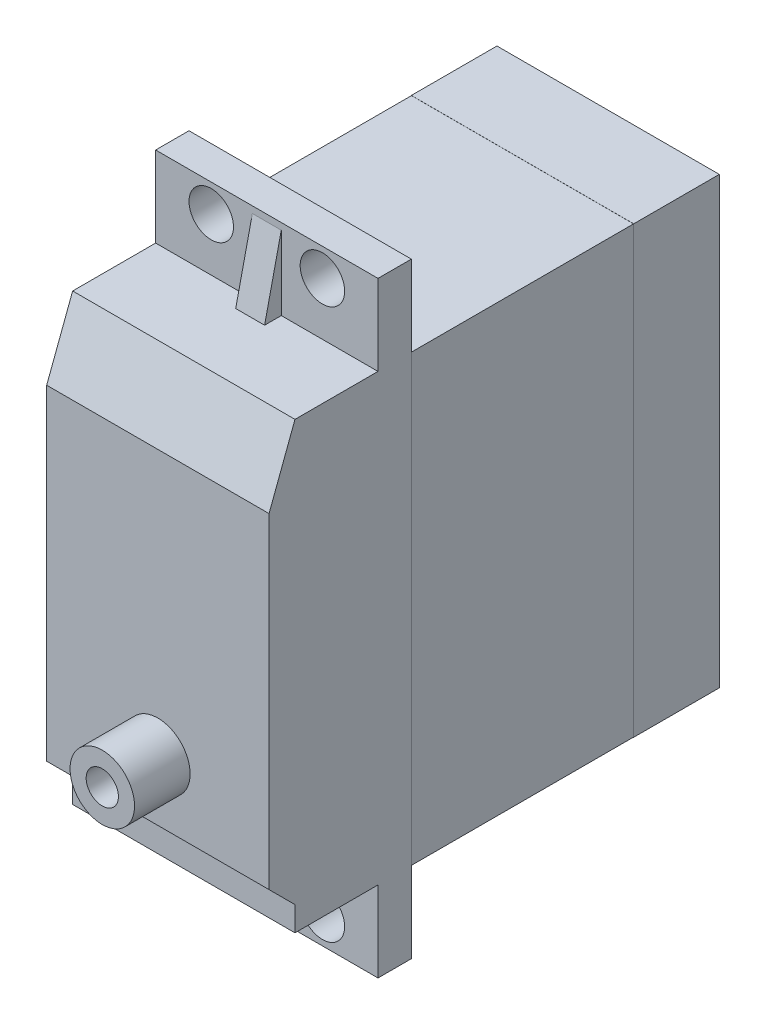
SolidWorks part; units mm, degrees
ref_plane "Front Plane" through (0, 0, 0) normal (1, 0, 0) x (0, 1, 0)
ref_plane "Top Plane" through (0, 0, 0) normal (0, 0, 1) x (0, 1, 0)
ref_plane "Right Plane" through (0, 0, 0) normal (0, 1, 0) x (-1, 0, 0)
sketch "Sketch1" plane through (0, 0, 0) normal (0, 0, 1) x (0, 1, 0)
  line L1 (-20, 10) -> (20, 10)
  line L2 (-20, 10) -> (-20, -10)
  line L3 (-20, -10) -> (20, -10)
  line L4 (20, 10) -> (20, -10)
  line L5 (-20, 10) -> (20, -10) construction
  line L6 (-20, -10) -> (20, 10) construction
  point P0 (0, 0)
  dimension "D1" = 20
  dimension "D2" = 40
extrude "Boss-Extrude1" add sketch "Sketch1" along normal blind 40.5
sketch "Sketch2" plane through (10, 0, 0) normal (1, 0, 0) x (0, 1, 0)
  line L0 (-20, 40.5) -> (-20, 0) construction
  line L1 (-20, 30.7) -> (-27.25, 30.7)
  line L2 (-20, 30.7) -> (-20, 27.7)
  line L3 (-20, 27.7) -> (-27.25, 27.7)
  line L4 (-27.25, 30.7) -> (-27.25, 27.7)
  line L5 (20, 40.5) -> (20, 0) construction
  line L6 (20, 30.7) -> (27.25, 30.7)
  line L7 (20, 30.7) -> (20, 27.7)
  line L8 (20, 27.7) -> (27.25, 27.7)
  line L9 (27.25, 30.7) -> (27.25, 27.7)
  line L10 (-20, 0) -> (20, 0) construction
  line L11 (20, 38.1665) -> (13.8263, 40.5)
  line L13 (13.8263, 40.5) -> (20, 40.5)
  line L14 (20, 40.5) -> (20, 38.1665)
  line L15 (-20, 38.1665) -> (-17.7986, 38.1665)
  line L16 (-17.7986, 38.1665) -> (-15.4651, 40.5)
  line L17 (-20, 40.5) -> (20, 40.5) construction
  line L18 (-15.4651, 40.5) -> (-20, 40.5)
  line L19 (-20, 40.5) -> (-20, 38.1665)
  line M10 (20, 0) -> (20, 40.5)
  line M11 (20, 40.5) -> (-20, 40.5)
  line M12 (-20, 40.5) -> (-20, 0)
  dimension "D1" = 27.7
  dimension "D2" = 3
  dimension "D3" = 7.25
  dimension "D4" = 54.5
  dimension "D5" = 135
  dimension "D6" = 3.3
  dimension "D7" = 5.1
  dimension "D8" = 6.6
extrude "Boss-Extrude2" add sketch "Sketch2" against normal up to surface (20 mm away) up to face at (-10, 0, 20.25)
sketch "Sketch3" plane through (0, 0, 30.7) normal (0, 0, 1) x (1, 0, 0)
  line L0 (-5, 24.75) -> (5, -24.75) construction
  circle A0 centre (-5, 24.75) radius 2
  circle A1 centre (5, 24.75) radius 2
  circle A2 centre (-5, -24.75) radius 2
  circle A3 centre (5, -24.75) radius 2
  dimension "D1" = 10
  dimension "D3" = 4
  dimension "D2" = 49.5
extrude "Cut-Extrude1" cut sketch "Sketch3" against normal up to surface (3 mm away) up to face at (0, -23.625, 27.7)
sketch "Sketch4" plane through (0, 0, 40.5) normal (0, 0, 1) x (1, 0, 0)
  line L0 (-10, -20) -> (10, -20) construction
  circle A0 centre (0, -10) radius 2.9
  circle A3 centre (0, -10) radius 1.45
  dimension "D1" = 10
  dimension "D2" = 5.8
  dimension "D3" = 2.9
extrude "Boss-Extrude3" add sketch "Sketch4" along normal blind 5 contours A0 region at (-2.818, -10, 40.5)
extrude "Cut-Extrude2" cut sketch "Sketch2<2>" against normal up to surface (20 mm away) contours L15 L16 M11 M12 | L11 M10 M11 region at (10, 17.9421, 39.7222) region at (10, -18.2486, 39.468) up to face at (-10, 0, 26.2167)
sketch "Sketch2<2>" plane through (10, 0, 0) normal (1, 0, 0) x (0, 1, 0) same geometry as "Sketch2"
sketch "Sketch5" plane through (0, 0, 27.7) normal (0, 0, -1) x (1, 0, 0)
  line L1 (-10, 20) -> (10, 20)
  line L2 (-10, 20) -> (-10, -20)
  line L3 (-10, -20) -> (10, -20)
  line L4 (10, 20) -> (10, -20)
  line L16 (-9.99, -19.99) -> (9.99, -19.99)
  line L17 (9.99, -19.99) -> (9.99, 19.99)
  line L18 (9.99, 19.99) -> (-9.99, 19.99)
  line L19 (-9.99, 19.99) -> (-9.99, -19.99)
  line L20 (-9.99, -19.99) -> (9.99, -19.99)
  line L21 (9.99, -19.99) -> (9.99, 19.99)
  line L22 (9.99, 19.99) -> (-9.99, 19.99)
  line L23 (-9.99, 19.99) -> (-9.99, -19.99)
  dimension "D1" = 0.01
extrude "Cut-Extrude3" cut sketch "Sketch5" along normal blind 20
sketch "Sketch6" plane through (0, 0, 0) normal (1, 0, 0) x (0, 1, 0)
  line L0 (-26.65, 30.7) -> (-20, 32.2)
  line L1 (-20, 30.7) -> (-27.25, 30.7) construction
  line L2 (-20, 38.1665) -> (-20, 30.7) construction
  line L3 (-20, 32.2) -> (-20, 30.7)
  line L4 (-20, 30.7) -> (-26.65, 30.7)
  line L5 (20, 32.2) -> (26.65, 30.7)
  line L6 (20, 38.1665) -> (20, 30.7) construction
  line L8 (20, 30.7) -> (20, 32.2)
  line L9 (26.65, 30.7) -> (20, 30.7)
  line L10 (-27.25, 30.7) -> (-27.25, 27.7) construction
  dimension "D1" = 0.6
  dimension "D2" = 1.5
extrude "Boss-Extrude5" add sketch "Sketch6" along normal blind 1.3 and the other way blind 1.3
sketch "Sketch7" plane through (0, -20, 0) normal (0, -1, 0) x (1, 0, 0)
  line L0 (10, 7.7) -> (-10, 7.7) construction
  line L1 (-3.15, 7.7) -> (3.15, 7.7)
  line L2 (-3.15, 7.7) -> (-3.15, 3.7)
  line L3 (-3.15, 3.7) -> (3.15, 3.7)
  line L4 (3.15, 7.7) -> (3.15, 3.7)
  line L5 (-3.15, 7.7) -> (3.15, 3.7) construction
  line L6 (-3.15, 3.7) -> (3.15, 7.7) construction
  point P0 (0, 5.7)
  point P5 (-0.3052, 5.1713)
  dimension "D1" = 6.3
  dimension "D2" = 4
extrude "Boss-Extrude6" add sketch "Sketch7" along normal blind 6
